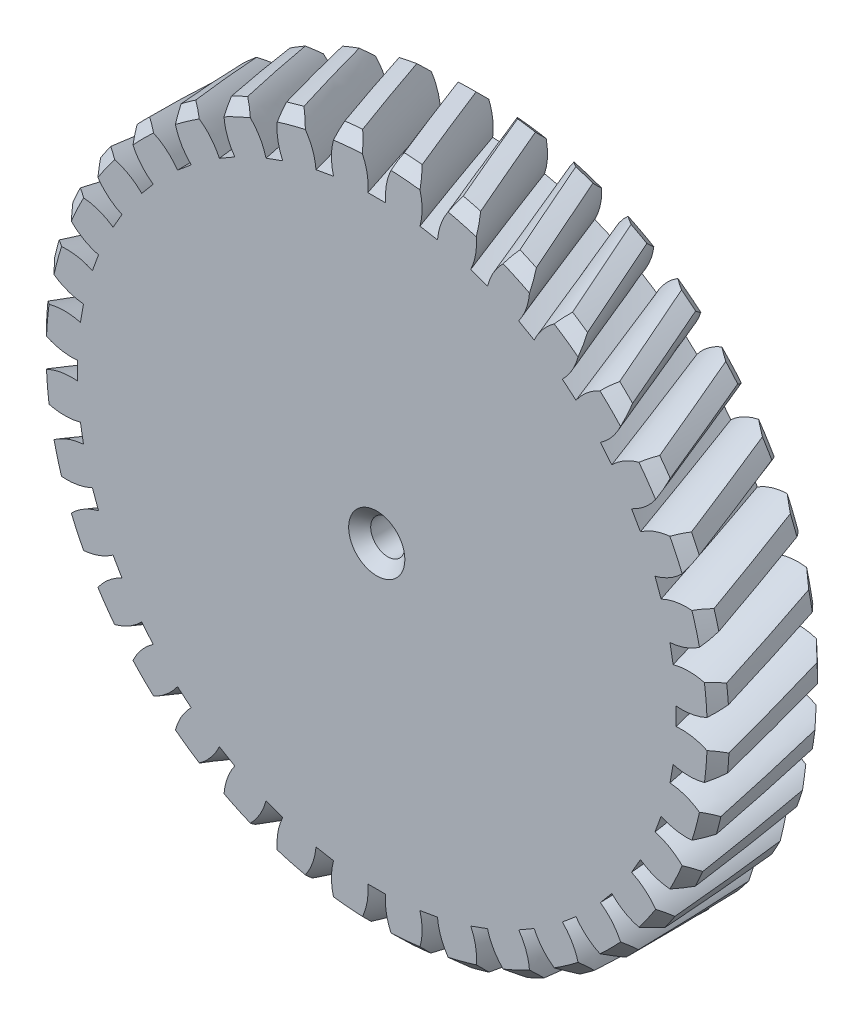
SolidWorks part; units mm, degrees
ref_plane "Front Plane" through (0, 0, 0) normal (1, 0, 0) x (0, 1, 0)
ref_plane "Top Plane" through (0, 0, 0) normal (0, 0, 1) x (0, 1, 0)
ref_plane "Right Plane" through (0, 0, 0) normal (0, 1, 0) x (-1, 0, 0)
sketch "Sketch5" plane through (0, 0, 0) normal (0, 0, 1) x (0, 1, 0)
  circle A0 centre (0, 0) radius 31
  circle A1 centre (0, 0) radius 1.55
  dimension "D1" = 62
  dimension "D2" = 3.1
extrude "Boss-Extrude1" add sketch "Sketch5" along normal blind 10
sketch "Sketch3" plane through (0, 0, 0) normal (0, 0, 1) x (0, 1, 0)
  line L0 (-4.75, 0) -> (-4.3361, 2.5035) construction
  line L1 (0, 0) -> (0, 4.3731) construction
  line L2 (4.75, 0) -> (4.3361, 2.5035) construction
  line L3 (-0.9247, 4.6591) -> (0, 5.0069) construction
  line L4 (2.375, -4.1136) -> (4.3361, -2.5035) construction
  line L5 (2.375, 4.1136) -> (4.3361, 2.5035) construction
  line L6 (-2.375, -4.1136) -> (0, -5.0069) construction
  line L7 (4.75, 0) -> (4.3361, -2.5035) construction
  line L8 (-4.75, 0) -> (-4.3361, -2.5035) construction
  line L9 (2.375, -4.1136) -> (0, -5.0069) construction
  line L10 (-3.5726, 3.1304) -> (-4.3361, 2.5035) construction
  line L11 (-2.375, -4.1136) -> (-4.3361, -2.5035) construction
  line L12 (2.375, 4.1136) -> (0, 5.0069) construction
  line L13 (-3.6926, 6.3958) -> (-2.4665, 13.8125)
  line L14 (-3.6926, 6.3958) -> (-10.7287, 9.0423)
  line L15 (3.6926, 6.3958) -> (10.7287, 9.0423)
  line L16 (3.6926, 6.3958) -> (2.4665, 13.8125)
  line L17 (7.3853, 0) -> (13.1953, -4.7702)
  line L18 (7.3853, 0) -> (13.1953, 4.7702)
  line L19 (3.6926, -6.3958) -> (2.4665, -13.8125)
  line L20 (3.6926, -6.3958) -> (10.7287, -9.0423)
  line L21 (-3.6926, -6.3958) -> (-10.7287, -9.0423)
  line L22 (-3.6926, -6.3958) -> (-2.4665, -13.8125)
  line L23 (-7.3853, 0) -> (-13.1953, 4.7702)
  line L24 (-7.3853, 0) -> (-13.1953, -4.7702)
  arc A2 (-3.5726, 3.1304) -> (-0.9247, 4.6591) centre (0, 0) ccw construction
  arc A3 (-2.4665, 13.8125) -> (2.4665, 13.8125) centre (0, 13.4048) cw
  arc A4 (10.7287, 9.0423) -> (13.1953, 4.7702) centre (11.6089, 6.7024) cw
  arc A5 (13.1953, -4.7702) -> (10.7287, -9.0423) centre (11.6089, -6.7024) cw
  arc A6 (2.4665, -13.8125) -> (-2.4665, -13.8125) centre (0, -13.4048) cw
  arc A7 (-10.7287, -9.0423) -> (-13.1953, -4.7702) centre (-11.6089, -6.7024) cw
  arc A8 (-13.1953, 4.7702) -> (-10.7287, 9.0423) centre (-11.6089, 6.7024) cw
  dimension "D1" = 9.5
  dimension "D2" = 14
  dimension "D3" = 2.5
  dimension "D4" = 6
extrude "Cut-Extrude1" cut sketch "Sketch3" along normal blind 3
fillet "Fillet1" radius 1 18 edges at (-10.1042, -3.0796, 0) (-10.1042, 3.0796, 0) (-7.7191, 7.2107, 0) (-7.9524, 13.7739, 0) (-2.3851, 10.2903, 0) (2.3851, 10.2903, 0) (7.9524, 13.7739, 0) (7.7191, 7.2107, 0) (10.1042, 3.0796, 0) (15.9048, 0, 0) (10.1042, -3.0796, 0) (7.7191, -7.2107, 0) (7.9524, -13.7739, 0) (2.3851, -10.2903, 0) (-2.3851, -10.2903, 0) (-7.9524, -13.7739, 0) (-7.7191, -7.2107, 0) (-15.9048, 0, 0)
chamfer "Chamfer1" distance 1 angle 45 3 edges at (1.55, 0, 10) (31, 0, 10) (31, 0, 0)
sketch "Sketch9" plane through (0, 0, 10) normal (0, 0, 1) x (1, 0, 0)
  circle A0 centre (0, 0) radius 31 construction
  circle A1 centre (0, 0) radius 31
curve "Helix/Spiral1" pitch 500 height 20 radius 31 left hand yes centre (0, 0, 10) axis (0, 0, -1) start towards (-1, 0, 0)
sketch "Sketch10" plane through (0, 0, 10) normal (0, 0, 1) x (1, 0, 0)
  line L0 (0, 0) -> (31, 0) construction
  line L1 (27.1695, 0.8085) -> (27.1695, -0.8085)
  circle A0 centre (0, 0) radius 31 construction
  arc A1 (30.9425, -1.8865) -> (30.9425, 1.8865) centre (0, 0) ccw
  arc A2 (27.1695, 0.8085) -> (30.9425, 1.8865) centre (27.6769, 6.1746) ccw
  arc A3 (27.1695, -0.8085) -> (30.9425, -1.8865) centre (27.6769, -6.1746) cw
  point P9 (27.1695, 0)
  dimension "D2" = 3.773
  dimension "D4" = 5.39
  dimension "D1" = 1.617
  dimension "D3" = 3.773
sweep "Cut-Sweep1" cut profiles "Sketch10" path "Helix/Spiral1" align with end faces yes
pattern_circular "CirPattern1" count 36 over 360 about axis through (0, 0, 10) along (0, 0, -1) of "Cut-Sweep1" reverse direction yes
